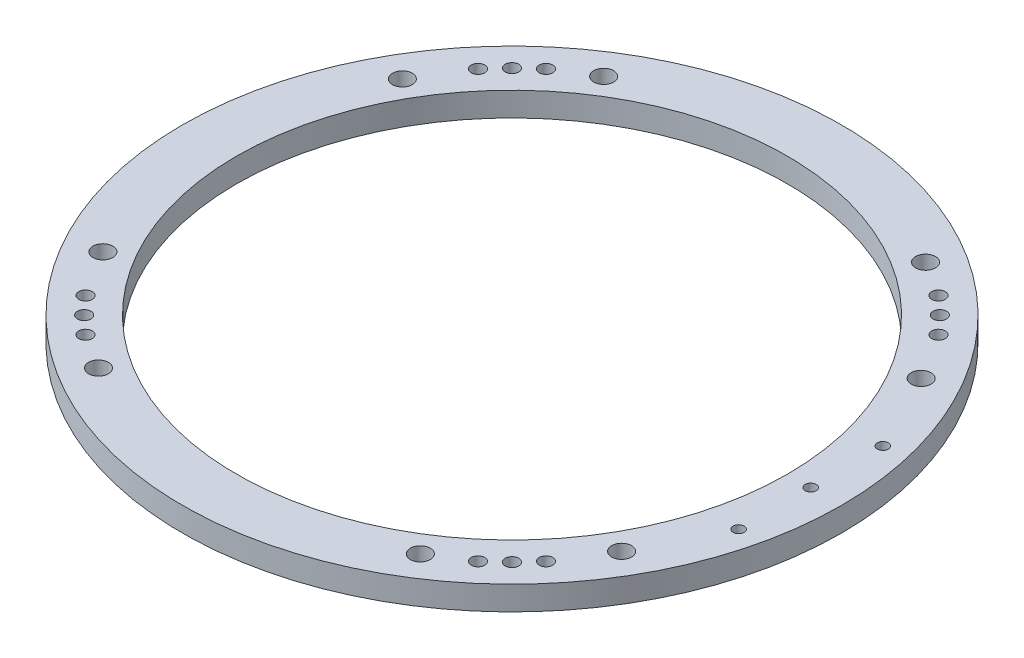
SolidWorks part; units mm, degrees
material "Oak"
ref_plane "Front Plane" through (0, 0, 0) normal (0, 0, 1) x (1, 0, 0)
ref_plane "Top Plane" through (0, 0, 0) normal (0, 1, 0) x (1, 0, 0)
ref_plane "Right Plane" through (0, 0, 0) normal (1, 0, 0) x (0, 0, -1)
sketch "Sketch1" plane through (0, 0, 0) normal (0, 0, 1) x (1, 0, 0)
  line L0 (0, 1125.8152) -> (0, -48874.1848) construction
  line L1 (145.5262, 1052.195) -> (152.4, 1052.195)
  line L9 (145.5262, 1064.895) -> (174.1012, 1064.895)
  line L10 (145.5262, 1064.895) -> (145.5262, 1052.195)
  line L11 (145.5262, 1052.195) -> (174.1012, 1052.195)
  line L12 (174.1012, 1064.895) -> (174.1012, 1052.195)
revolve "Revolve1" add sketch "Sketch1" angle 360 about L0 region at (159.8137, 1058.545, 0)
hole_wizard "9/32 (0.28125) Diameter Hole1" positions "Sketch9" profile "Sketch10" hole size "9/32" standard "ANSI Inch" end condition through all
sketch "Sketch9" plane through (0, 1052.195, 0) normal (0, -1, 0) x (-1, 0, 0)
  line L0 (0, 0) -> (113.0054, 113.0054) construction
  line L3 (0, 0) -> (103.6677, 121.6282) construction
  arc A0 (103.6677, 121.6282) -> (121.6282, 103.6677) centre (0, 0) cw
  circle A1 centre (0, 0) radius 159.8137 construction
  point P0 (103.6677, 121.6282)
  point P2 (121.6282, 103.6677)
  point P15 (113.0054, 113.0054)
sketch "Sketch10" plane through (-103.6677, 1052.195, -121.6282) normal (1, 0, 0) x (0, 0, -1)
  line L0 (0, 0) -> (0, 12.7)
  line L1 (0, 12.7) -> (3.5719, 12.7)
  line L2 (3.5719, 12.7) -> (3.5719, 0)
  line L5 (3.5719, 0) -> (0, 0)
  line L11 (0, -6.35) -> (0, 107.95) construction
  dimension "Thru Hole Dia." = 7.1437
  dimension "Thru Hole Depth" = 12.7
pattern_circular "CirPattern1" count 4 over 360 about axis through (0, 1125.8152, 0) along (0, 1, 0) of "9/32 (0.28125) Diameter Hole1"
ref_plane "Plane1" through (0, 1058.545, 0) normal (0, 1, 0) x (1, 0, 0)
hole_wizard "M5 Clearance Hole1" positions "Sketch14" profile "Sketch15" hole size "M5" standard "ANSI Metric" end condition through all
sketch "Sketch14" plane through (0, 1064.895, 0) normal (0, 1, 0) x (1, 0, 0)
  point P9 (157.7975, -38.1)
  point P12 (157.7975, 0)
  point P14 (157.7975, 38.1)
sketch "Sketch15" plane through (157.7975, 1064.895, 38.1) normal (1, 0, 0) x (0, 0, 1)
  line L0 (0, 0) -> (0, 12.7)
  line L1 (0, 12.7) -> (2.9, 12.7)
  line L2 (2.9, 12.7) -> (2.9, 0)
  line L5 (2.9, 0) -> (0, 0)
  line L11 (0, -6.35) -> (0, 107.95) construction
  dimension "Thru Hole Dia." = 5.8
  dimension "Thru Hole Depth" = 12.7
hole_wizard "Z (0.413) Diameter Hole1" positions "Sketch16" profile "Sketch17" hole size "Z" standard "ANSI Inch" end condition through all
sketch "Sketch16" plane through (0, 1064.895, 0) normal (0, 1, 0) x (1, 0, 0)
  line L0 (-137.0279, -79.1131) -> (137.0279, 79.1131) construction
  line L4 (137.0279, -79.1131) -> (-137.0279, 79.1131) construction
  line L6 (0, 0) -> (0, 158.2262) construction
  line L8 (-85.0149, -133.4467) -> (85.0149, 133.4467) construction
  line L11 (-85.0149, 133.4467) -> (85.0149, -133.4467) construction
  circle A0 centre (0, 0) radius 158.2262 construction
  circle A1 centre (0, 0) radius 145.5262 construction
  point P0 (-137.0279, -79.1131)
  point P2 (137.0279, -79.1131)
  point P4 (137.0279, 79.1131)
  point P6 (-137.0279, 79.1131)
  point P37 (-85.0149, 133.4467)
  point P39 (85.0149, 133.4467)
  point P41 (85.0149, -133.4467)
  point P43 (-85.0149, -133.4467)
  dimension "D2" = 12.7
  dimension "D1" = 120
  dimension "D3" = 65
sketch "Sketch17" plane through (-137.0279, 1064.895, 79.1131) normal (1, 0, 0) x (0, 0, 1)
  line L0 (0, 0) -> (0, 12.7)
  line L1 (0, 12.7) -> (5.2451, 12.7)
  line L2 (5.2451, 12.7) -> (5.2451, 0)
  line L5 (5.2451, 0) -> (0, 0)
  line L11 (0, -6.35) -> (0, 107.95) construction
  dimension "Thru Hole Dia." = 10.4902
  dimension "Thru Hole Depth" = 12.7
sketch "Sketch18" plane through (0, 1064.895, 0) normal (0, 1, 0) x (1, 0, 0)
  circle A5 centre (-103.6677, 121.6282) radius 1.5875
  circle A6 centre (-113.0054, 113.0054) radius 1.5875
  circle A7 centre (-121.6282, 103.6677) radius 1.5875
  circle A10 centre (103.6677, 121.6282) radius 1.5875
  circle A11 centre (113.0054, 113.0054) radius 1.5875
  circle A12 centre (121.6282, 103.6677) radius 1.5875
  circle A14 centre (-121.6282, -103.6677) radius 1.5875
  circle A37 centre (-113.0054, -113.0054) radius 1.5875
  circle A38 centre (-103.6677, -121.6282) radius 1.5875
  circle A39 centre (103.6677, -121.6282) radius 1.5875
  circle A40 centre (113.0054, -113.0054) radius 1.5875
  circle A41 centre (121.6282, -103.6677) radius 1.5875
  circle A53 centre (103.6677, 121.6282) radius 3.5719
  circle A54 centre (103.6677, 121.6282) radius 3.5719
  circle A55 centre (113.0054, 113.0054) radius 3.5719
  circle A56 centre (113.0054, 113.0054) radius 3.5719
  circle A57 centre (103.6677, -121.6282) radius 3.5719
  circle A58 centre (103.6677, -121.6282) radius 3.5719
  circle A59 centre (-121.6282, -103.6677) radius 3.5719
  circle A60 centre (-121.6282, -103.6677) radius 3.5719
  circle A61 centre (-103.6677, -121.6282) radius 3.5719
  circle A62 centre (-103.6677, -121.6282) radius 3.5719
  circle A63 centre (-113.0054, -113.0054) radius 3.5719
  circle A64 centre (-113.0054, -113.0054) radius 3.5719
  circle A65 centre (-103.6677, 121.6282) radius 3.5719
  circle A66 centre (-103.6677, 121.6282) radius 3.5719
  circle A67 centre (-121.6282, 103.6677) radius 3.5719
  circle A68 centre (-121.6282, 103.6677) radius 3.5719
  circle A69 centre (-113.0054, 113.0054) radius 3.5719
  circle A70 centre (-113.0054, 113.0054) radius 3.5719
  circle A73 centre (113.0054, -113.0054) radius 3.5719
  circle A74 centre (113.0054, -113.0054) radius 3.5719
  circle A75 centre (121.6282, -103.6677) radius 3.5719
  circle A76 centre (121.6282, -103.6677) radius 3.5719
  circle A77 centre (121.6282, 103.6677) radius 3.5719
  circle A78 centre (121.6282, 103.6677) radius 3.5719
  dimension "D13" = 3.175
  dimension "D14" = 0
  dimension "D15" = 0
  dimension "D16" = 0
  dimension "D17" = 0
  dimension "D18" = 0
  dimension "D19" = 0
  dimension "D20" = 0
  dimension "D21" = 0
  dimension "D22" = 0
  dimension "D24" = 0
  dimension "D25" = 0
  dimension "D26" = 0
extrude "Boss-Extrude1" [suppressed] add sketch "Sketch18" against normal up to surface (12.7 mm away) up to face at (-137.0279, 1052.195, 84.3582)
